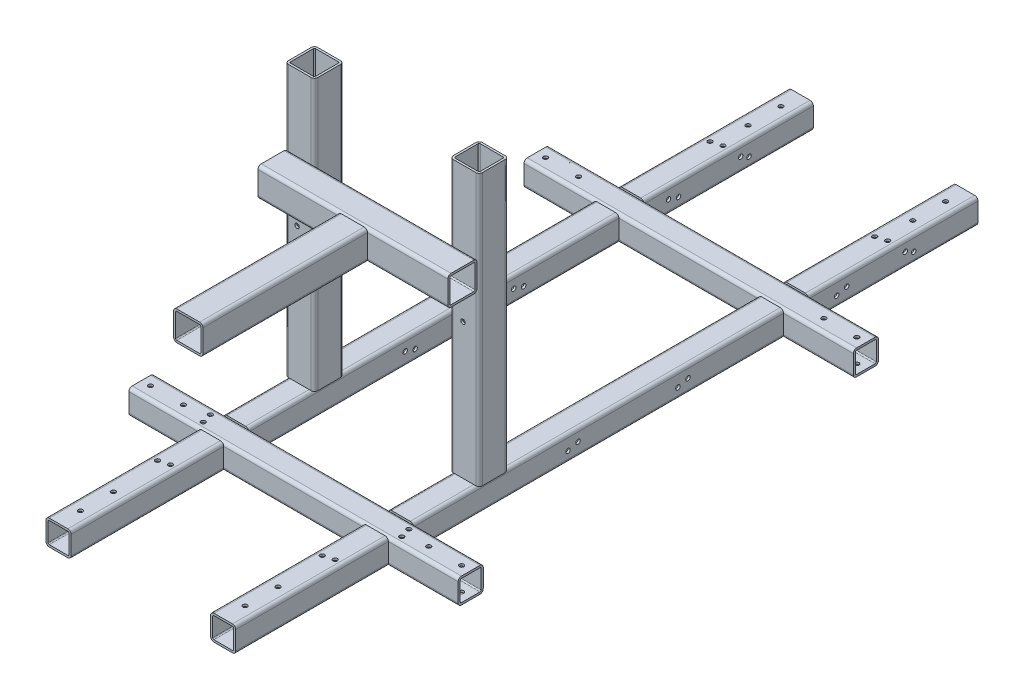
SolidWorks part; units mm, degrees
material "Alumina"
ref_plane "Front Plane" through (0, 0, 0) normal (0, 0, 1) x (1, 0, 0)
ref_plane "Top Plane" through (0, 0, 0) normal (0, 1, 0) x (1, 0, 0)
ref_plane "Right Plane" through (0, 0, 0) normal (1, 0, 0) x (0, 0, -1)
ref_plane "Bottom Face" through (0, 0, 0) normal (0, 1, 0) x (1, 0, 0)
ref_plane "Top Face" through (0, 38.1, 0) normal (0, 1, 0) x (1, 0, 0)
ref_plane "Mid Plane" through (0, 19.05, 0) normal (0, 1, 0) x (1, 0, 0)
ref_plane "Front Face" through (0, 0, 500) normal (0, 0, 1) x (1, 0, 0)
ref_plane "Back Face" through (0, 0, -500) normal (0, 0, 1) x (1, 0, 0)
ref_plane "Left Face" through (250, 0, 0) normal (1, 0, 0) x (0, 0, -1)
ref_plane "Right Face" through (-250, 0, 0) normal (1, 0, 0) x (0, 0, -1)
ref_plane "Divider Plane" through (0, 0, 140) normal (0, 0, 1) x (1, 0, 0)
ref_plane "Max Height Plane" through (0, 450, 0) normal (0, 1, 0) x (1, 0, 0)
ref_plane "Electronics Box Plane" through (0, 338.1, 0) normal (0, 1, 0) x (1, 0, 0)
sketch "Sketch2" plane through (250, 0, 0) normal (1, 0, 0) x (0, 0, -1)
  line L0 (330, 38.1) -> (-330, 38.1) construction
  line L5 (330, 0) -> (-330, 0) construction
  line L6 (0, 220) -> (0, -220) construction
  line L7 (-314.05, 38.1) -> (-285.95, 38.1)
  line L8 (-280.95, 33.1) -> (-280.95, 5)
  line L9 (-315.875, 33.1) -> (-315.875, 5)
  line L10 (-314.05, 3.175) -> (-285.95, 3.175)
  line L11 (-285.95, 0) -> (-314.05, 0)
  line L12 (-319.05, 5) -> (-319.05, 33.1)
  line L13 (-300, 38.1) -> (-300, 0) construction
  line L14 (-319.05, 19.05) -> (-280.95, 19.05) construction
  line L15 (-284.125, 5) -> (-284.125, 33.1)
  line L16 (-285.95, 34.925) -> (-314.05, 34.925)
  line L17 (-300, 34.925) -> (-300, 3.175) construction
  line L18 (-315.875, 19.05) -> (-284.125, 19.05) construction
  arc A0 (-285.95, 38.1) -> (-280.95, 33.1) centre (-285.95, 33.1) cw
  arc A1 (-280.95, 5) -> (-285.95, 0) centre (-285.95, 5) cw
  arc A2 (-314.05, 0) -> (-319.05, 5) centre (-314.05, 5) cw
  arc A3 (-319.05, 33.1) -> (-314.05, 38.1) centre (-314.05, 33.1) cw
  arc A4 (-315.875, 5) -> (-314.05, 3.175) centre (-314.05, 5) ccw
  arc A5 (-285.95, 3.175) -> (-284.125, 5) centre (-285.95, 5) ccw
  arc A6 (-284.125, 33.1) -> (-285.95, 34.925) centre (-285.95, 33.1) ccw
  arc A7 (-314.05, 34.925) -> (-315.875, 33.1) centre (-314.05, 33.1) ccw
  point P20 (-300, 19.05)
  point P39 (-300, 19.05)
  dimension "D1" = 5
  dimension "D2" = 300
  dimension "D3" = 3.175
extrude "Front Cross-Car Member" add sketch "Sketch2" against normal up to surface (500 mm away) up to plane "Right Face"
sketch "Sketch5" plane through (250, 0, 0) normal (1, 0, 0) x (0, 0, -1)
  line L0 (285.95, 38.1) -> (314.05, 38.1)
  line L1 (319.05, 33.1) -> (319.05, 5)
  line L2 (314.05, 0) -> (285.95, 0)
  line L3 (280.95, 5) -> (280.95, 33.1)
  line L4 (300, 38.1) -> (300, 0) construction
  line L5 (280.95, 19.05) -> (319.05, 19.05) construction
  line L6 (285.95, 34.925) -> (314.05, 34.925)
  line L7 (315.875, 33.1) -> (315.875, 5)
  line L8 (314.05, 3.175) -> (285.95, 3.175)
  line L9 (284.125, 5) -> (284.125, 33.1)
  line L10 (300, 34.925) -> (300, 3.175) construction
  line L11 (284.125, 19.05) -> (315.875, 19.05) construction
  line L12 (330, 0) -> (-330, 0) construction
  line L14 (330, 38.1) -> (-330, 38.1) construction
  line L15 (0, 220) -> (0, -220) construction
  arc A0 (314.05, 38.1) -> (319.05, 33.1) centre (314.05, 33.1) cw
  arc A1 (319.05, 5) -> (314.05, 0) centre (314.05, 5) cw
  arc A2 (285.95, 0) -> (280.95, 5) centre (285.95, 5) cw
  arc A3 (280.95, 33.1) -> (285.95, 38.1) centre (285.95, 33.1) cw
  arc A4 (314.05, 34.925) -> (315.875, 33.1) centre (314.05, 33.1) cw
  arc A5 (315.875, 5) -> (314.05, 3.175) centre (314.05, 5) cw
  arc A6 (285.95, 3.175) -> (284.125, 5) centre (285.95, 5) cw
  arc A7 (284.125, 33.1) -> (285.95, 34.925) centre (285.95, 33.1) cw
  point P32 (300, 19.05)
  point P33 (300, 19.05)
  dimension "D2" = 5
  dimension "D1" = 3.175
  dimension "D3" = 300
extrude "Back Cross-Car Member" add sketch "Sketch5" against normal up to surface (500 mm away) separate body up to plane "Right Face"
sketch "Sketch6" plane through (0, 0, -500) normal (0, 0, 1) x (1, 0, 0)
  line L0 (110.95, 38.1) -> (139.05, 38.1)
  line L1 (144.05, 33.1) -> (144.05, 5)
  line L2 (109.125, 33.1) -> (109.125, 5)
  line L3 (110.95, 3.175) -> (139.05, 3.175)
  line L4 (139.05, 0) -> (110.95, 0)
  line L5 (105.95, 5) -> (105.95, 33.1)
  line L6 (125, 38.1) -> (125, 0) construction
  line L7 (105.95, 19.05) -> (144.05, 19.05) construction
  line L8 (140.875, 5) -> (140.875, 33.1)
  line L9 (139.05, 34.925) -> (110.95, 34.925)
  line L10 (125, 34.925) -> (125, 3.175) construction
  line L11 (109.125, 19.05) -> (140.875, 19.05) construction
  line L12 (330, 38.1) -> (-330, 38.1) construction
  line L13 (330, 0) -> (-330, 0) construction
  line L14 (0, -220) -> (0, 220) construction
  arc A0 (139.05, 38.1) -> (144.05, 33.1) centre (139.05, 33.1) cw
  arc A1 (144.05, 5) -> (139.05, 0) centre (139.05, 5) cw
  arc A2 (110.95, 0) -> (105.95, 5) centre (110.95, 5) cw
  arc A3 (105.95, 33.1) -> (110.95, 38.1) centre (110.95, 33.1) cw
  arc A4 (109.125, 5) -> (110.95, 3.175) centre (110.95, 5) ccw
  arc A5 (139.05, 3.175) -> (140.875, 5) centre (139.05, 5) ccw
  arc A6 (140.875, 33.1) -> (139.05, 34.925) centre (139.05, 33.1) ccw
  arc A7 (110.95, 34.925) -> (109.125, 33.1) centre (110.95, 33.1) ccw
  point P16 (125, 19.05)
  point P33 (125, 19.05)
  dimension "D1" = 5
  dimension "D2" = 3.175
  dimension "D3" = 125
extrude "Back Left Along-Car Member" add sketch "Sketch6" along normal blind 180.95 and the other way blind 76.2
extrude "Middle Left Along-Car Member" add sketch "Sketch6<2>" along normal blind 561.9 from offset 219.05
sketch "Sketch6<2>" plane through (0, 0, -500) normal (0, 0, 1) x (1, 0, 0) same geometry as "Sketch6"
extrude "Front Left Along-Car Member" add sketch "Sketch6<3>" along normal blind 231.75 from offset 819.05
sketch "Sketch6<3>" plane through (0, 0, -500) normal (0, 0, 1) x (1, 0, 0) same geometry as "Sketch6"
sketch "Sketch7" plane through (0, 0, -500) normal (0, 0, 1) x (1, 0, 0)
  line L0 (-139.05, 38.1) -> (-110.95, 38.1)
  line L1 (-105.95, 33.1) -> (-105.95, 5)
  line L2 (-140.875, 33.1) -> (-140.875, 5)
  line L3 (-139.05, 3.175) -> (-110.95, 3.175)
  line L4 (-110.95, 0) -> (-139.05, 0)
  line L5 (-144.05, 5) -> (-144.05, 33.1)
  line L6 (-125, 38.1) -> (-125, 0) construction
  line L7 (-144.05, 19.05) -> (-105.95, 19.05) construction
  line L8 (-109.125, 5) -> (-109.125, 33.1)
  line L9 (-110.95, 34.925) -> (-139.05, 34.925)
  line L10 (-125, 34.925) -> (-125, 3.175) construction
  line L11 (-140.875, 19.05) -> (-109.125, 19.05) construction
  line L12 (330, 38.1) -> (-330, 38.1) construction
  line L13 (330, 0) -> (-330, 0) construction
  line L14 (0, -220) -> (0, 220) construction
  arc A0 (-110.95, 38.1) -> (-105.95, 33.1) centre (-110.95, 33.1) cw
  arc A1 (-105.95, 5) -> (-110.95, 0) centre (-110.95, 5) cw
  arc A2 (-139.05, 0) -> (-144.05, 5) centre (-139.05, 5) cw
  arc A3 (-144.05, 33.1) -> (-139.05, 38.1) centre (-139.05, 33.1) cw
  arc A4 (-140.875, 5) -> (-139.05, 3.175) centre (-139.05, 5) ccw
  arc A5 (-110.95, 3.175) -> (-109.125, 5) centre (-110.95, 5) ccw
  arc A6 (-109.125, 33.1) -> (-110.95, 34.925) centre (-110.95, 33.1) ccw
  arc A7 (-139.05, 34.925) -> (-140.875, 33.1) centre (-139.05, 33.1) ccw
  point P16 (-125, 19.05)
  point P33 (-125, 19.05)
  dimension "D1" = 5
  dimension "D2" = 3.175
  dimension "D3" = 125
extrude "Back Right Along-Car Member" add sketch "Sketch7" along normal blind 180.95 and the other way blind 76.2
extrude "Middle Right Along-Car Member" add sketch "Sketch7<2>" along normal blind 561.9 from offset 219.05
sketch "Sketch7<2>" plane through (0, 0, -500) normal (0, 0, 1) x (1, 0, 0) same geometry as "Sketch7"
extrude "Front Right Along-Car Member" add sketch "Sketch7<3>" along normal blind 231.75 from offset 819.05
sketch "Sketch7<3>" plane through (0, 0, -500) normal (0, 0, 1) x (1, 0, 0) same geometry as "Sketch7"
sketch "Sketch8" plane through (0, 38.1, 0) normal (0, 1, 0) x (1, 0, 0)
  line L0 (-142.225, -140) -> (-107.775, -140)
  line L1 (-102.775, -145) -> (-102.775, -179.45)
  line L2 (-144.05, -145) -> (-144.05, -179.45)
  line L3 (-142.225, -181.275) -> (-107.775, -181.275)
  line L4 (-107.775, -184.45) -> (-142.225, -184.45)
  line L5 (-147.225, -179.45) -> (-147.225, -145)
  line L6 (-125, -140) -> (-125, -184.45) construction
  line L7 (-147.225, -162.225) -> (-102.775, -162.225) construction
  line L8 (-105.95, -179.45) -> (-105.95, -145)
  line L9 (-107.775, -143.175) -> (-142.225, -143.175)
  line L10 (-125, -143.175) -> (-125, -181.275) construction
  line L11 (-144.05, -162.225) -> (-105.95, -162.225) construction
  line L12 (-220, -140) -> (220, -140) construction
  line L13 (0, -20.955) -> (0, 20.955) construction
  arc A0 (-107.775, -140) -> (-102.775, -145) centre (-107.775, -145) cw
  arc A1 (-102.775, -179.45) -> (-107.775, -184.45) centre (-107.775, -179.45) cw
  arc A2 (-142.225, -184.45) -> (-147.225, -179.45) centre (-142.225, -179.45) cw
  arc A3 (-147.225, -145) -> (-142.225, -140) centre (-142.225, -145) cw
  arc A4 (-144.05, -179.45) -> (-142.225, -181.275) centre (-142.225, -179.45) ccw
  arc A5 (-107.775, -181.275) -> (-105.95, -179.45) centre (-107.775, -179.45) ccw
  arc A6 (-105.95, -145) -> (-107.775, -143.175) centre (-107.775, -145) ccw
  arc A7 (-142.225, -143.175) -> (-144.05, -145) centre (-142.225, -145) ccw
  point P16 (-125, -162.225)
  point P33 (-125, -162.225)
  dimension "D1" = 5
  dimension "D2" = 3.175
  dimension "D3" = 44.45
  dimension "D4" = 125
extrude "Right Vertical Member" add sketch "Sketch8" along normal up to surface (411.9 mm away) up to plane "Max Height Plane"
sketch "Sketch10" plane through (0, 38.1, 0) normal (0, 1, 0) x (1, 0, 0)
  line L0 (107.775, -140) -> (142.225, -140)
  line L1 (147.225, -145) -> (147.225, -179.45)
  line L2 (105.95, -145) -> (105.95, -179.45)
  line L3 (107.775, -181.275) -> (142.225, -181.275)
  line L4 (142.225, -184.45) -> (107.775, -184.45)
  line L5 (102.775, -179.45) -> (102.775, -145)
  line L6 (125, -140) -> (125, -184.45) construction
  line L7 (102.775, -162.225) -> (147.225, -162.225) construction
  line L8 (144.05, -179.45) -> (144.05, -145)
  line L9 (142.225, -143.175) -> (107.775, -143.175)
  line L10 (125, -143.175) -> (125, -181.275) construction
  line L11 (105.95, -162.225) -> (144.05, -162.225) construction
  line L12 (-220, -140) -> (220, -140) construction
  line L13 (0, -247.5) -> (0, 247.5) construction
  arc A0 (142.225, -140) -> (147.225, -145) centre (142.225, -145) cw
  arc A1 (147.225, -179.45) -> (142.225, -184.45) centre (142.225, -179.45) cw
  arc A2 (107.775, -184.45) -> (102.775, -179.45) centre (107.775, -179.45) cw
  arc A3 (102.775, -145) -> (107.775, -140) centre (107.775, -145) cw
  arc A4 (105.95, -179.45) -> (107.775, -181.275) centre (107.775, -179.45) ccw
  arc A5 (142.225, -181.275) -> (144.05, -179.45) centre (142.225, -179.45) ccw
  arc A6 (144.05, -145) -> (142.225, -143.175) centre (142.225, -145) ccw
  arc A7 (107.775, -143.175) -> (105.95, -145) centre (107.775, -145) ccw
  point P16 (125, -162.225)
  point P33 (125, -162.225)
  dimension "D1" = 5
  dimension "D2" = 3.175
  dimension "D3" = 44.45
  dimension "D4" = 125
extrude "Left Vertical Member" add sketch "Sketch10" along normal up to surface (411.9 mm away) up to plane "Max Height Plane"
sketch "Sketch11" plane through (250, 0, 0) normal (1, 0, 0) x (0, 0, -1)
  line L0 (-223.9, 338.1) -> (-189.45, 338.1)
  line L1 (-184.45, 333.1) -> (-184.45, 298.65)
  line L2 (-225.725, 333.1) -> (-225.725, 298.65)
  line L3 (-223.9, 296.825) -> (-189.45, 296.825)
  line L4 (-189.45, 293.65) -> (-223.9, 293.65)
  line L5 (-228.9, 298.65) -> (-228.9, 333.1)
  line L6 (-206.675, 338.1) -> (-206.675, 293.65) construction
  line L7 (-228.9, 315.875) -> (-184.45, 315.875) construction
  line L8 (-187.625, 298.65) -> (-187.625, 333.1)
  line L9 (-189.45, 334.925) -> (-223.9, 334.925)
  line L10 (-206.675, 334.925) -> (-206.675, 296.825) construction
  line L11 (-225.725, 315.875) -> (-187.625, 315.875) construction
  line L13 (330, 338.1) -> (-330, 338.1) construction
  line L14 (-184.45, 450) -> (-184.45, 38.1) construction
  arc A0 (-189.45, 338.1) -> (-184.45, 333.1) centre (-189.45, 333.1) cw
  arc A1 (-184.45, 298.65) -> (-189.45, 293.65) centre (-189.45, 298.65) cw
  arc A2 (-223.9, 293.65) -> (-228.9, 298.65) centre (-223.9, 298.65) cw
  arc A3 (-228.9, 333.1) -> (-223.9, 338.1) centre (-223.9, 333.1) cw
  arc A4 (-225.725, 298.65) -> (-223.9, 296.825) centre (-223.9, 298.65) ccw
  arc A5 (-189.45, 296.825) -> (-187.625, 298.65) centre (-189.45, 298.65) ccw
  arc A6 (-187.625, 333.1) -> (-189.45, 334.925) centre (-189.45, 333.1) ccw
  arc A7 (-223.9, 334.925) -> (-225.725, 333.1) centre (-223.9, 333.1) ccw
  point P16 (-206.675, 315.875)
  point P33 (-206.675, 315.875)
  dimension "D1" = 5
  dimension "D2" = 3.175
  dimension "D3" = 44.45
extrude "Upper Cross-Car Member" add sketch "Sketch11" against normal blind 288.1 from offset 105.95 offset against normal yes
sketch "Sketch12" plane through (0, 0, 140) normal (0, 0, 1) x (1, 0, 0)
  line L0 (-17.225, 338.1) -> (17.225, 338.1)
  line L1 (22.225, 333.1) -> (22.225, 298.65)
  line L2 (-19.05, 333.1) -> (-19.05, 298.65)
  line L3 (-17.225, 296.825) -> (17.225, 296.825)
  line L4 (17.225, 293.65) -> (-17.225, 293.65)
  line L5 (-22.225, 298.65) -> (-22.225, 333.1)
  line L6 (0, 338.1) -> (0, 293.65) construction
  line L7 (-22.225, 315.875) -> (22.225, 315.875) construction
  line L8 (19.05, 298.65) -> (19.05, 333.1)
  line L9 (17.225, 334.925) -> (-17.225, 334.925)
  line L10 (0, 334.925) -> (0, 296.825) construction
  line L11 (-19.05, 315.875) -> (19.05, 315.875) construction
  line L12 (330, 338.1) -> (-330, 338.1) construction
  line L13 (0, -247.5) -> (0, 247.5) construction
  arc A0 (17.225, 338.1) -> (22.225, 333.1) centre (17.225, 333.1) cw
  arc A1 (22.225, 298.65) -> (17.225, 293.65) centre (17.225, 298.65) cw
  arc A2 (-17.225, 293.65) -> (-22.225, 298.65) centre (-17.225, 298.65) cw
  arc A3 (-22.225, 333.1) -> (-17.225, 338.1) centre (-17.225, 333.1) cw
  arc A4 (-19.05, 298.65) -> (-17.225, 296.825) centre (-17.225, 298.65) ccw
  arc A5 (17.225, 296.825) -> (19.05, 298.65) centre (17.225, 298.65) ccw
  arc A6 (19.05, 333.1) -> (17.225, 334.925) centre (17.225, 333.1) ccw
  arc A7 (-17.225, 334.925) -> (-19.05, 333.1) centre (-17.225, 333.1) ccw
  point P16 (0, 315.875)
  point P33 (0, 315.875)
  dimension "D1" = 5
  dimension "D2" = 3.175
  dimension "D3" = 44.45
extrude "E-Box Platform Base" add sketch "Sketch12" along normal blind 250 from surface starting at face at (0, 315.875, 228.9)
sketch "Sketch13" plane through (0, 0, 140) normal (0, 0, -1) x (-1, 0, 0)
  circle A2 centre (129.225, 244.1) radius 3.3782
  circle A3 centre (-122.775, 244.1) radius 3.3782
extrude "Cut-Extrude1" cut sketch "Sketch13" against normal up to surface (44.45 mm away) up to face at (125, 124.95, 184.45)
sketch "Sketch14" plane through (0, 38.1, 0) normal (0, 1, 0) x (1, 0, 0)
  circle A0 centre (-132.62, -392.85) radius 3.3782
  circle A1 centre (-117.38, -388.45) radius 3.3782
  circle A2 centre (-152.9, -292.38) radius 3.3782
  circle A3 centre (-148.5, -307.62) radius 3.3782
  circle A8 centre (152.9, -307.62) radius 3.3782
  circle A9 centre (148.5, -292.38) radius 3.3782
  circle A10 centre (117.38, -392.85) radius 3.3782
  circle A11 centre (132.62, -388.45) radius 3.3782
extrude "Cut-Extrude2" cut sketch "Sketch14" against normal up to surface (38.1 mm away) up to face at (125, 0, 434.925)
sketch "Sketch16" plane through (105.95, 0, 0) normal (-1, 0, 0) x (0, 0, 1)
  circle A0 centre (-478.5, 15.24) radius 3.3782
  circle A1 centre (-465.8, 21.59) radius 3.3782
extrude "Cut-Extrude4" cut sketch "Sketch16" along normal up to surface and the other way up to surface up to face at (-144.05, 19.05, -447.625) other way up to face at (144.05, 19.05, -447.625)
sketch "Sketch17" plane through (-144.05, 0, 0) normal (-1, 0, 0) x (0, 0, 1)
  circle A1 centre (43.5864, 20.25) radius 3.3782
  circle A2 centre (28.3464, 15.85) radius 3.3782
  circle A3 centre (-356.2832, 20.25) radius 3.3782
  circle A4 centre (-371.5232, 15.85) radius 3.3782
  circle A5 centre (-121.1547, 20.25) radius 3.3782
  circle A6 centre (-136.3947, 15.85) radius 3.3782
sketch "Sketch18" plane through (0, 38.1, 0) normal (0, 1, 0) x (1, 0, 0)
  circle A0 centre (-132.62, 446) radius 3.3782
  circle A1 centre (-117.38, 450.4) radius 3.3782
  circle A2 centre (117.38, 446) radius 3.3782
  circle A3 centre (132.62, 450.4) radius 3.3782
sketch "Sketch19" plane through (144.05, 0, 0) normal (1, 0, 0) x (0, 0, -1)
  circle A0 centre (-46.3207, 15.85) radius 3.3782
  circle A1 centre (-31.0807, 20.25) radius 3.3782
  circle A2 centre (376.8433, 20.25) radius 3.3782
  circle A3 centre (361.6033, 15.85) radius 3.3782
  circle A4 centre (120.5766, 15.85) radius 3.3782
  circle A5 centre (135.8166, 20.25) radius 3.3782
extrude "Cut-Extrude5" cut sketch "Sketch17" against normal up to surface (38.1 mm away) up to face at (-105.95, 19.05, 0)
extrude "Cut-Extrude6" cut sketch "Sketch18" against normal up to surface (38.1 mm away) up to face at (-125, 0, -447.625)
extrude "Cut-Extrude7" cut sketch "Sketch19" against normal up to surface (38.1 mm away) up to face at (105.95, 19.05, 0)
sketch "Sketch20" plane through (0, 38.1, 0) normal (0, 1, 0) x (1, 0, 0)
  circle A0 centre (236.2063, -300) radius 3.38
  circle A1 centre (186.2063, -300) radius 3.38
  circle A2 centre (125, -517.6063) radius 3.38
  circle A3 centre (125, -467.6062) radius 3.38
  circle A4 centre (-125, -517.6063) radius 3.38
  circle A5 centre (-125, -467.6063) radius 3.38
  circle A6 centre (-186.2062, -300) radius 3.38
  circle A7 centre (-236.2062, -300) radius 3.38
  circle A8 centre (236.2062, 300) radius 3.38
  circle A9 centre (186.2062, 300) radius 3.38
  circle A10 centre (-186.2063, 300) radius 3.38
  circle A11 centre (-236.2063, 300) radius 3.38
  circle A12 centre (125, 496.0062) radius 3.38
  circle A13 centre (125, 546.0063) radius 3.38
  circle A14 centre (-125, 496.0062) radius 3.38
  circle A15 centre (-125, 546.0063) radius 3.38
extrude "Cut-Extrude8" cut sketch "Sketch20" against normal up to surface (38.1 mm away) up to face at (-132.62, 0, -449.3782)
equation "\"D1@Front Face\" = \"frameLength@Master Assembly.SLDASM\" / 2"
equation "\"D1@Back Face\" = \"frameLength@Master Assembly.SLDASM\" / 2"
equation "\"D1@Left Face\"=\"frameWidth@Master Assembly.SLDASM\"/2"
equation "\"D1@Right Face\" = \"frameWidth@Master Assembly.SLDASM\" / 2"
equation "\"D1@Top Face\"=\"frameTubeStockHeight@Master Assembly.SLDASM\""
equation "\"D2@Sketch2\"=\"frameMemberDistLength@Master Assembly.SLDASM\"/2"
equation "\"D3@Sketch2\"=\"frameTubeStockWallThickness@Master Assembly.SLDASM\""
equation "\"D1@Sketch5\"=\"frameTubeStockWallThickness@Master Assembly.SLDASM\""
equation "\"D3@Sketch5\"=\"frameMemberDistLength@Master Assembly.SLDASM\"/2"
equation "\"D3@Sketch6\"=\"frameMemberDistWidth@Master Assembly.SLDASM\"/2"
equation "\"D1@Back Left Along-Car Member\"=( \"frameLength@Master Assembly.Assembly\" - \"frameMemberDistLength@Master Assembly.Assembly\" - \"frameTubeStockHeight@Master Assembly.Assembly\" )  / 2"
equation "\"D19@Middle Left Along-Car Member\" = ( \"frameLength@Master Assembly.SLDASM\" - \"frameMemberDistLength@Master Assembly.SLDASM\" + \"frameTubeStockHeight@Master Assembly.SLDASM\" ) / 2"
equation "\"D1@Middle Left Along-Car Member\"=\"frameMemberDistLength@Master Assembly.SLDASM\" - \"frameTubeStockHeight@Master Assembly.SLDASM\""
equation "\"D19@Front Left Along-Car Member\"=( \"frameLength@Master Assembly.SLDASM\" - \"frameMemberDistLength@Master Assembly.SLDASM\" )  / 2 + \"frameMemberDistLength@Master Assembly.SLDASM\" + \"frameTubeStockHeight@Master Assembly.SLDASM\" / 2"
equation "\"D1@Front Left Along-Car Member\" =  ( \"frameLength@Master Assembly.Assembly\" - \"frameMemberDistLength@Master Assembly.Assembly\" - \"frameTubeStockHeight@Master Assembly.Assembly\" )  / 2 + 2in"
equation "\"D3@Sketch7\"=\"frameMemberDistWidth@Master Assembly.SLDASM\"/2"
equation "\"D1@Back Right Along-Car Member\"=(\"frameLength@Master Assembly.SLDASM\" - \"frameMemberDistLength@Master Assembly.SLDASM\" - \"frameTubeStockHeight@Master Assembly.SLDASM\")  / 2"
equation "\"D19@Middle Right Along-Car Member\" = ( \"frameLength@Master Assembly.SLDASM\" - \"frameMemberDistLength@Master Assembly.SLDASM\" + \"frameTubeStockHeight@Master Assembly.SLDASM\" ) / 2"
equation "\"D1@Middle Right Along-Car Member\"=\"frameMemberDistLength@Master Assembly.SLDASM\" - \"frameTubeStockHeight@Master Assembly.SLDASM\""
equation "\"D19@Front Right Along-Car Member\"=( \"frameLength@Master Assembly.SLDASM\" - \"frameMemberDistLength@Master Assembly.SLDASM\" )  / 2 + \"frameMemberDistLength@Master Assembly.SLDASM\" + \"frameTubeStockHeight@Master Assembly.SLDASM\" / 2"
equation "\"D1@Front Right Along-Car Member\"=( \"frameLength@Master Assembly.Assembly\" - \"frameMemberDistLength@Master Assembly.Assembly\" - \"frameTubeStockHeight@Master Assembly.Assembly\" )  / 2 + 2in"
equation "\"D1@Divider Plane\"= \"frameDividerPlaneOffset@Master Assembly.SLDASM\""
equation "\"D3@Sketch8\"=1.75in"
equation "\"D4@Sketch8\"=\"frameMemberDistWidth@Master Assembly.SLDASM\"/2"
equation "\"D1@Max Height Plane\" = \"frameHeight@Master Assembly.SLDASM\""
equation "\"D4@Sketch10\"=\"frameMemberDistWidth@Master Assembly.SLDASM\"/2"
equation "\"D1@Electronics Box Plane\" = \"eboxPlaneHeight@Master Assembly.SLDASM\""
equation "\"D19@Upper Cross-Car Member\" = ( \"frameWidth@Master Assembly.SLDASM\" - \"frameMemberDistWidth@Master Assembly.SLDASM\" - \"frameTubeStockHeight@Master Assembly.SLDASM\" ) / 2"
equation "\"D1@Upper Cross-Car Member\" = \"frameMemberDistWidth@Master Assembly.SLDASM\" + \"frameTubeStockHeight@Master Assembly.SLDASM\""
equation "\"D19@E-Box Platform Base\"=2in * 2"
equation "\"D2@Sketch6\"=\"frameTubeStockWallThickness@Master Assembly.SLDASM\""
equation "\"D2@Sketch7\"=\"frameTubeStockWallThickness@Master Assembly.SLDASM\""
equation "\"D2@Sketch8\"=\"frameTubeStockWallThickness@Master Assembly.SLDASM\""
equation "\"D2@Sketch10\"=\"frameTubeStockWallThickness@Master Assembly.SLDASM\""
equation "\"D3@Sketch11\"=1.75in"
equation "\"D2@Sketch11\"=\"frameTubeStockWallThickness@Master Assembly.SLDASM\""
equation "\"D3@Sketch12\"=1.75in"
equation "\"D2@Sketch12\"=\"frameTubeStockWallThickness@Master Assembly.SLDASM\""
equation "\"D3@Sketch10\"=1.75in"
